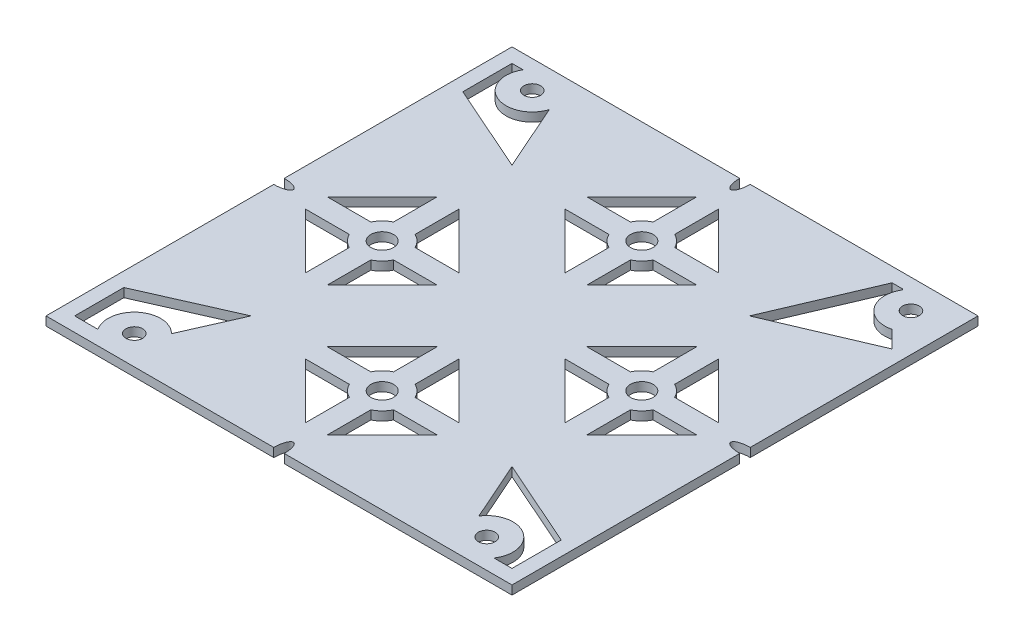
SolidWorks part; units mm, degrees
material "ABS"
ref_plane "Front Plane" through (0, 0, 0) normal (0, 0, 1) x (1, 0, 0)
ref_plane "Top Plane" through (0, 0, 0) normal (0, 1, 0) x (1, 0, 0)
ref_plane "Right Plane" through (0, 0, 0) normal (1, 0, 0) x (0, 0, -1)
sketch "Sketch1" plane through (0, 0, 0) normal (0, 1, 0) x (1, 0, 0)
  line L1 (0, 0) -> (97.6, 0)
  line L2 (0, 0) -> (0, 97.6)
  line L3 (0, 97.6) -> (97.6, 97.6)
  line L4 (97.6, 0) -> (97.6, 97.6)
  dimension "D1" = 97.6
  dimension "D2" = 97.6
extrude "Boss-Extrude1" add sketch "Sketch1" along normal blind 1.85
sketch "Sketch2" plane through (0, 0, 0) normal (0, -1, 0) x (-1, 0, 0)
  line L0 (-97.6, 97.6) -> (0, 0) construction
  line L1 (-97.6, 0) -> (0, 97.6) construction
  line L2 (-48.8, 97.6) -> (-48.8, 0) construction
  line L3 (-97.6, 97.6) -> (0, 97.6) construction
  line L4 (0, 0) -> (-97.6, 0) construction
  line L5 (-97.6, 48.8) -> (0, 48.8) construction
  line L6 (-97.6, 0) -> (-97.6, 97.6) construction
  line L7 (0, 97.6) -> (0, 0) construction
sketch "Sketch3" plane through (0, 0, 0) normal (0, -1, 0) x (1, 0, 0)
  line L0 (97.6, -97.6) -> (0, -97.6) construction
  line L1 (97.6, 0) -> (97.6, -97.6) construction
  line L2 (0, -97.6) -> (0, 0) construction
  line L3 (0, 0) -> (97.6, 0) construction
  line L4 (97.6, -94.6) -> (0, -94.6) construction
  line L5 (3, -97.6) -> (3, 0) construction
  line L6 (3, -94.6) -> (5.3161, -94.6)
  line L7 (3, -94.6) -> (3, -84.3)
  line L8 (3, -84.3) -> (21.4728, -76.1272)
  line L9 (97.6, 0) -> (0, -97.6) construction
  line L10 (21.4728, -76.1272) -> (13.3, -94.6)
  line L11 (21.4728, -21.4728) -> (13.3, -3)
  line L12 (3, -3) -> (13.3, -3)
  line L13 (0, -3) -> (97.6, -3) construction
  line L14 (3, -13.3) -> (3, -3)
  line L15 (3, -3) -> (7.8732, -3)
  line L16 (3, -13.3) -> (21.4728, -21.4728)
  line L17 (97.6, -97.6) -> (0, 0) construction
  line L18 (0, -97.6) -> (0, 0) construction
  line L19 (16.1614, -10.109) -> (21.4728, -21.4728) construction
  line L20 (94.6, -97.6) -> (94.6, 0) construction
  line L21 (94.6, -3) -> (94.6, -13.3)
  line L22 (94.6, -3) -> (84.3, -3)
  line L23 (94.6, -13.3) -> (76.1272, -21.4728)
  line L24 (76.1272, -21.4728) -> (84.3, -3)
  line L25 (94.6, -82.6) -> (73.6741, -73.6741)
  line L26 (73.6741, -73.6741) -> (82.6, -94.6)
  line L27 (94.6, -82.6) -> (82.6, -94.6) construction
  line L28 (94.6, -82.6) -> (91.0273, -86.1727)
  line L29 (82.6, -94.6) -> (85.1169, -94.6)
  line L30 (3, -94.6) -> (13.3, -94.6) construction
  circle A0 centre (89.66, -91.5) radius 1.25
  circle A1 centre (10.05, -91.8) radius 1.25
  circle A2 centre (12.45, -6.05) radius 1.25
  circle A3 centre (86.25, -6.05) radius 1.25
  circle A4 centre (89.66, -91.5) radius 5.5
  circle A5 centre (10.05, -91.8) radius 5.5
  circle A6 centre (12.45, -6.05) radius 5.5
  circle A7 centre (86.25, -6.05) radius 5.5
  dimension "D1" = 6.1
  dimension "D9" = 3
  dimension "D16" = 3
  dimension "D20" = 2.5
  dimension "D21" = 11
  dimension "D23" = 11
  dimension "D24" = 2.5
  dimension "D26" = 11
  dimension "D27" = 11
  dimension "D2" = 7.94
  dimension "D3" = 5.8
  dimension "D4" = 10.05
  dimension "D5" = 6.05
  dimension "D6" = 12.45
  dimension "D7" = 6.05
  dimension "D8" = 11.35
  dimension "D10" = 3
  dimension "D11" = 10.3
  dimension "D12" = 20.2
  dimension "D13" = 3
  dimension "D14" = 10.3
  dimension "D15" = 20.2
  dimension "D17" = 10.3
  dimension "D18" = 22.75
  dimension "D19" = 15
  dimension "D22" = 10.3
  dimension "D25" = 20.2
extrude "Cut-Extrude1" cut sketch "Sketch3" against normal blind 10 contours A2 | A1 | A1 | A5 L8 L7 L6 | A4 L28 L25 L26 L29 | A3 | A7 L24 L23 L21 L22 | A6 L15 L14 L16 | A0 region at (11.5662, 0, -84.2704) region at (10.6634, 0, -12.5774) region at (86.5986, 0, -12.9459) region at (83.266, 0, -83.1897) region at (10.05, 0, -91.8) region at (12.45, 0, -6.05) region at (86.25, 0, -6.05)
fillet "Fillet1" radius 0.2 1 edges at (85.1169, 0.925, -94.6)
sketch "Sketch5" plane through (0, 0, 0) normal (0, -1, 0) x (1, 0, 0)
  line L0 (78.0601, -69.3344) -> (24.4532, -15.7275) construction
  line L1 (15.9101, -24.6358) -> (67.2589, -75.9846) construction
  line L2 (97.6, -97.6) -> (0, 0) construction
  line L3 (25.594, -80.7317) -> (80.9701, -25.3556) construction
  line L4 (71.5743, -17.3) -> (16.8047, -72.0696) construction
  line L5 (97.6, 0) -> (0, -97.6) construction
  line L6 (51.05, -89.7671) -> (51.05, -80.6171)
  line L7 (46.55, -89.7671) -> (46.55, -80.6171)
  line L8 (48.8, -97.6) -> (48.8, 0) construction
  line L9 (51.05, -89.7671) -> (62.5825, -78.2346)
  line L10 (62.5825, -78.2346) -> (53.4325, -78.2346)
  line L11 (44.1675, -78.2346) -> (35.0175, -78.2346)
  line L12 (35.0175, -78.2346) -> (46.55, -89.7671)
  line L13 (48.8, -78.2346) -> (36.0473, -78.2346) construction
  line L14 (48.8, -73.7346) -> (36.0473, -73.7346) construction
  line L15 (44.1675, -73.7346) -> (35.0175, -73.7346)
  line L16 (46.55, -71.3521) -> (46.55, -62.2021)
  line L17 (53.4325, -73.7346) -> (62.5825, -73.7346)
  line L18 (51.05, -71.3521) -> (51.05, -62.2021)
  line L19 (62.5825, -73.7346) -> (51.05, -62.2021)
  line L20 (46.55, -62.2021) -> (35.0175, -73.7346)
  line L21 (48.8, -48.8) -> (-2.5605, -100.1605) construction
  line L22 (48.8, -48.8) -> (97.6, 0) construction
  line L23 (97.6, -97.6) -> (0, 0) construction
  line L24 (73.7346, -48.8) -> (73.7346, -36.0473) construction
  line L25 (78.2346, -48.8) -> (78.2346, -36.0473) construction
  line L26 (62.2021, -46.55) -> (73.7346, -35.0175)
  line L27 (73.7346, -62.5825) -> (62.2021, -51.05)
  line L28 (71.3521, -51.05) -> (62.2021, -51.05)
  line L29 (73.7346, -53.4325) -> (73.7346, -62.5825)
  line L30 (71.3521, -46.55) -> (62.2021, -46.55)
  line L31 (73.7346, -44.1675) -> (73.7346, -35.0175)
  line L32 (78.2346, -35.0175) -> (89.7671, -46.55)
  line L33 (78.2346, -44.1675) -> (78.2346, -35.0175)
  line L34 (78.2346, -62.5825) -> (78.2346, -53.4325)
  line L35 (89.7671, -51.05) -> (78.2346, -62.5825)
  line L36 (89.7671, -46.55) -> (80.6171, -46.55)
  line L37 (89.7671, -51.05) -> (80.6171, -51.05)
  line L38 (48.8, -19.3654) -> (61.5527, -19.3654) construction
  line L39 (48.8, -23.8654) -> (61.5527, -23.8654) construction
  line L40 (23.8654, -48.8) -> (23.8654, -61.5527) construction
  line L41 (19.3654, -48.8) -> (19.3654, -61.5527) construction
  line L42 (46.55, -7.8329) -> (46.55, -16.9829)
  line L43 (51.05, -7.8329) -> (51.05, -16.9829)
  line L44 (46.55, -7.8329) -> (35.0175, -19.3654)
  line L45 (35.0175, -19.3654) -> (44.1675, -19.3654)
  line L46 (53.4325, -19.3654) -> (62.5825, -19.3654)
  line L47 (62.5825, -19.3654) -> (51.05, -7.8329)
  line L48 (53.4325, -23.8654) -> (62.5825, -23.8654)
  line L49 (51.05, -26.2479) -> (51.05, -35.3979)
  line L50 (44.1675, -23.8654) -> (35.0175, -23.8654)
  line L51 (46.55, -26.2479) -> (46.55, -35.3979)
  line L52 (35.0175, -23.8654) -> (46.55, -35.3979)
  line L53 (51.05, -35.3979) -> (62.5825, -23.8654)
  line L54 (35.3979, -51.05) -> (23.8654, -62.5825)
  line L55 (23.8654, -35.0175) -> (35.3979, -46.55)
  line L56 (26.2479, -46.55) -> (35.3979, -46.55)
  line L57 (23.8654, -44.1675) -> (23.8654, -35.0175)
  line L58 (26.2479, -51.05) -> (35.3979, -51.05)
  line L59 (23.8654, -53.4325) -> (23.8654, -62.5825)
  line L60 (19.3654, -62.5825) -> (7.8329, -51.05)
  line L61 (19.3654, -53.4325) -> (19.3654, -62.5825)
  line L62 (19.3654, -35.0175) -> (19.3654, -44.1675)
  line L63 (7.8329, -46.55) -> (19.3654, -35.0175)
  line L64 (7.8329, -51.05) -> (16.9829, -51.05)
  line L65 (7.8329, -46.55) -> (16.9829, -46.55)
  line L66 (49.9, -97.6) -> (47.7, -97.6)
  line L67 (97.6, -97.6) -> (0, -97.6) construction
  line L68 (97.6, -48.8) -> (97.6, -49.9)
  line L69 (97.6, 0) -> (97.6, -97.6) construction
  line L70 (97.6, -48.8) -> (97.6, -47.7)
  line L71 (0, -49.9) -> (0, -48.8)
  line L72 (0, -97.6) -> (0, 0) construction
  line L73 (0, -48.8) -> (0, -47.7)
  line L74 (48.8, 0) -> (49.9, 0)
  line L75 (0, 0) -> (97.6, 0) construction
  line L76 (48.8, 0) -> (47.7, 0)
  circle A0 centre (48.8, -75.9846) radius 2.375
  circle A1 centre (48.8, -75.9846) radius 5.15
  circle A2 centre (75.9846, -48.8) radius 5.15
  circle A3 centre (75.9846, -48.8) radius 2.375
  circle A4 centre (48.8, -21.6154) radius 2.375
  circle A5 centre (48.8, -21.6154) radius 5.15
  circle A6 centre (21.6154, -48.8) radius 5.15
  circle A7 centre (21.6154, -48.8) radius 2.375
  ellipse E0 centre (48.8, -97.6) end of major axis (48.8, -94.6046) minor radius 1.1
  ellipse E1 centre (97.6, -48.8) end of major axis (94.5962, -48.8) minor radius 1.1
  ellipse E2 centre (0, -48.8) end of major axis (3, -48.8) minor radius 1.1
  ellipse E3 centre (48.8, 0) end of major axis (48.8, -3) minor radius 1.1
  line M15 (0, 0) -> (0, -97.6)
  line M16 (0, -97.6) -> (97.6, -97.6)
  line M17 (97.6, -97.6) -> (97.6, 0)
  line M18 (97.6, 0) -> (0, 0)
  dimension "D5" = 9.15
  dimension "D7" = 4.75
  dimension "D8" = 10.3
  dimension "D1" = 6.17
  dimension "D2" = 6.17
  dimension "D3" = 6.17
  dimension "D4" = 6.17
  dimension "D6" = 2.25
  dimension "D9" = 2.25
  dimension "D10" = 1.1
  dimension "D11" = 1.1
  dimension "D12" = 1.1
  dimension "D13" = 3
  dimension "D14" = 2.25
  dimension "D15" = 2.25
  dimension "D16" = 3
extrude "Cut-Extrude2" cut sketch "Sketch5" against normal blind 10 contours A1 L6 L9 L10 | A1 L11 L12 L7 | A0 | A1 L17 L19 L18 | A1 L16 L20 L15 | L61 A6 L64 L60 | L58 A6 L59 L54 | L57 A6 L56 L55 | L65 A6 L62 L63 | A7 | A3 | L37 A2 L34 L35 | L29 A2 L28 L27 | L30 A2 L31 L26 | L33 A2 L36 L32 | A5 L42 L44 L45 | A5 L46 L47 L43 | A5 L49 L53 L48 | A5 L50 L52 L51 | E0 M16 | E3 M18 | E1 M17 | E2 M15 | A4 region at (55.0576, 0, -82.2422) region at (42.5424, 0, -82.2422) region at (42.5424, 0, -69.7269) region at (55.0576, 0, -69.7269) region at (69.7269, 0, -42.5424) region at (69.7269, 0, -55.0576) region at (82.2422, 0, -42.5424) region at (82.2422, 0, -55.0576) region at (42.5424, 0, -15.3578) region at (55.0576, 0, -15.3578) region at (42.5424, 0, -27.8731) region at (55.0576, 0, -27.8731) region at (27.8731, 0, -55.0576) region at (15.3578, 0, -55.0576) region at (27.8731, 0, -42.5424) region at (15.3578, 0, -42.5424) region at (48.8, 0, -96.3287) region at (96.3251, 0, -48.8) region at (1.2732, 0, -48.8) region at (48.8, 0, -1.2732) region at (48.8, 0, -75.9846) region at (75.9846, 0, -48.8) region at (21.6154, 0, -48.8)
sketch "Sketch6" plane through (0, 0, 0) normal (0, -1, 0) x (1, 0, 0)
  circle A0 centre (12.45, -6.05) radius 1.75
  circle A1 centre (86.25, -6.05) radius 1.75
  circle A2 centre (10.05, -91.8) radius 1.75
  circle A3 centre (89.66, -91.5) radius 1.75
extrude "Cut-Extrude3" cut sketch "Sketch6" against normal through all
